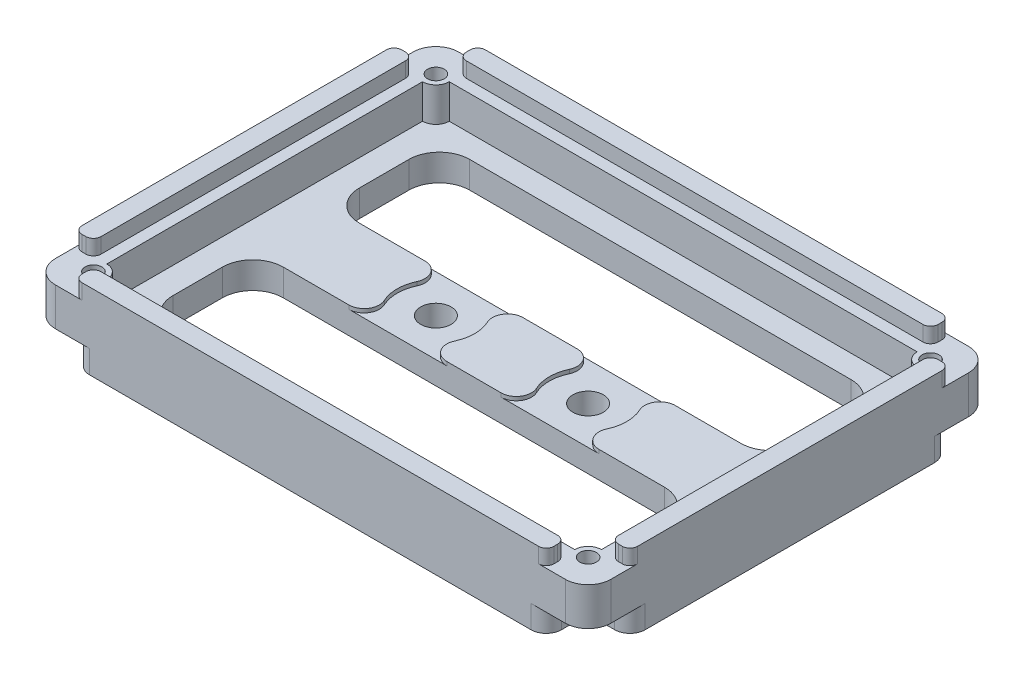
SolidWorks part; units mm, degrees
ref_plane "Plan de face" through (0, 0, 0) normal (0, 0, 1) x (1, 0, 0)
ref_plane "Plan de dessus" through (0, 0, 0) normal (0, 1, 0) x (1, 0, 0)
ref_plane "Plan de droite" through (0, 0, 0) normal (1, 0, 0) x (0, 0, -1)
sketch "Esquisse1" plane through (0, 0, 0) normal (0, 1, 0) x (1, 0, 0)
  line L1 (-32.5, -22.5) -> (32.5, -22.5) construction
  line L2 (-32.5, -22.5) -> (-32.5, 22.5) construction
  line L3 (-32.5, 22.5) -> (32.5, 22.5) construction
  line L4 (32.5, -22.5) -> (32.5, 22.5) construction
  line L5 (-32.5, -22.5) -> (32.5, 22.5) construction
  line L6 (-32.5, 22.5) -> (32.5, -22.5) construction
  line L7 (-31.0556, -21.5) -> (31.0556, -21.5)
  line L8 (-31.0556, -21.5) -> (-31.0556, 21.5)
  line L9 (-31.0556, 21.5) -> (31.0556, 21.5)
  line L10 (31.0556, -21.5) -> (31.0556, 21.5)
  line L11 (-31.0556, -21.5) -> (31.0556, 21.5) construction
  line L12 (-31.0556, 21.5) -> (31.0556, -21.5) construction
  line L13 (-36.5, -26.5) -> (36.5, -26.5)
  line L14 (-36.5, -26.5) -> (-36.5, 26.5)
  line L15 (-36.5, 26.5) -> (36.5, 26.5)
  line L16 (36.5, -26.5) -> (36.5, 26.5)
  line L17 (-36.5, -26.5) -> (36.5, 26.5) construction
  line L18 (-36.5, 26.5) -> (36.5, -26.5) construction
  circle A0 centre (-32.5, 22.5) radius 1.1
  circle A1 centre (32.5, 22.5) radius 1.1
  circle A2 centre (32.5, -22.5) radius 1.1
  circle A3 centre (-32.5, -22.5) radius 1.1
  point P0 (0, 0)
  point P10 (0, 0)
  point P15 (0, 0)
  dimension "D3" = 2.2
  dimension "D1" = 65
  dimension "D2" = 45
  dimension "D4" = 1
  dimension "D5" = 4
  dimension "D6" = 4
extrude "Boss.-Extru.1" add sketch "Esquisse1" along normal blind 10
sketch "Esquisse2" plane through (0, 0, 0) normal (0, -1, 0) x (1, 0, 0)
  line L1 (-36.5, -26.5) -> (36.5, -26.5)
  line L2 (-36.5, -26.5) -> (-36.5, 26.5)
  line L3 (-36.5, 26.5) -> (36.5, 26.5)
  line L4 (36.5, -26.5) -> (36.5, 26.5)
  line L5 (-36.5, -26.5) -> (36.5, 26.5) construction
  line L6 (-36.5, 26.5) -> (36.5, -26.5) construction
  point P0 (0, 0)
extrude "Boss.-Extru.2" add sketch "Esquisse2" against normal blind 4
sketch "Esquisse3" plane through (0, 0, 0) normal (0, -1, 0) x (1, 0, 0)
  line L1 (-36.5, 26.5) -> (-31, 26.5)
  line L2 (-36.5, 26.5) -> (-36.5, 21)
  line L3 (-36.5, 21) -> (-31, 21)
  line L4 (-31, 26.5) -> (-31, 21)
  line L5 (36.5, 26.5) -> (31, 26.5)
  line L6 (36.5, 26.5) -> (36.5, 21)
  line L7 (36.5, 21) -> (31, 21)
  line L8 (31, 26.5) -> (31, 21)
  line L9 (36.5, -26.5) -> (31, -26.5)
  line L10 (36.5, -26.5) -> (36.5, -21)
  line L11 (36.5, -21) -> (31, -21)
  line L12 (31, -26.5) -> (31, -21)
  line L13 (-36.5, -26.5) -> (-31, -26.5)
  line L14 (-36.5, -26.5) -> (-36.5, -21)
  line L15 (-36.5, -21) -> (-31, -21)
  line L16 (-31, -26.5) -> (-31, -21)
  dimension "D1" = 5.5
extrude "Enlèv. mat.-Extru.1" cut sketch "Esquisse3" against normal blind 3
sketch "Esquisse4" plane through (0, 4, 0) normal (0, 1, 0) x (1, 0, 0)
  circle A0 centre (-32.5, 22.5) radius 1.1
  circle A1 centre (32.5, 22.5) radius 1.1
  circle A2 centre (32.5, -22.5) radius 1.1
  circle A3 centre (-32.5, -22.5) radius 1.1
  dimension "D1" = 2.2
extrude "Enlèv. mat.-Extru.2" cut sketch "Esquisse4" against normal blind 5
fillet "Congé3" radius 3 4 edges at (-36.5, 6.5, 26.5) (-36.5, 6.5, -26.5) (36.5, 6.5, -26.5) (36.5, 6.5, 26.5)
sketch "Esquisse5" plane through (0, 4, 0) normal (0, 1, 0) x (1, 0, 0)
  line L0 (-10, 0) -> (10, 0) construction
  line L1 (31.0556, 21.5) -> (-31.0556, 21.5) construction
  line L2 (-29.0556, 5) -> (29.0556, 5)
  line L3 (-29.0556, 5) -> (-29.0556, 19.5)
  line L4 (-29.0556, 19.5) -> (29.0556, 19.5)
  line L5 (29.0556, 5) -> (29.0556, 19.5)
  line L6 (-29.0556, 5) -> (29.0556, 19.5) construction
  line L7 (-29.0556, 19.5) -> (29.0556, 5) construction
  line L8 (-29.0556, -5) -> (29.0556, -5)
  line L9 (-29.0556, -5) -> (-29.0556, -19.5)
  line L10 (-29.0556, -19.5) -> (29.0556, -19.5)
  line L11 (29.0556, -5) -> (29.0556, -19.5)
  line L12 (-29.0556, -5) -> (29.0556, -19.5) construction
  line L13 (-29.0556, -19.5) -> (29.0556, -5) construction
  line L14 (-31.0556, -21.5) -> (31.0556, -21.5) construction
  line L15 (-31.0556, 21.5) -> (-31.0556, -21.5) construction
  line L16 (31.0556, -21.5) -> (31.0556, 21.5) construction
  line L17 (31.0556, -21.5) -> (31.0556, 21.5) construction
  circle A0 centre (-10, 0) radius 2
  circle A1 centre (10, 0) radius 2
  point P3 (0, 0)
  point P6 (0, 12.25)
  point P11 (0, -12.25)
  dimension "D1" = 4
  dimension "D2" = 2
  dimension "D3" = 2
  dimension "D4" = 2
  dimension "D5" = 2
  dimension "D6" = 2
  dimension "D7" = 2
  dimension "D8" = 5
  dimension "D9" = 5
  dimension "D10" = 20
extrude "Enlèv. mat.-Extru.3" cut sketch "Esquisse5" against normal blind 5
fillet "Congé4" radius 4 8 edges at (-29.0556, 2, 19.5) (29.0556, 2, 5) (29.0556, 2, 19.5) (-29.0556, 2, 5) (29.0556, 2, -5) (29.0556, 2, -19.5) (-29.0556, 2, -19.5) (-29.0556, 2, -5)
fillet "Congé5" radius 2 12 edges at (-31, 1.5, -21) (-31, 1.5, 21) (31, 1.5, 21) (31, 1.5, -21) (-36.5, 1.5, 21) (-31, 1.5, 26.5) (31, 1.5, 26.5) (36.5, 1.5, 21) (36.5, 1.5, -21) (31, 1.5, -26.5) (-31, 1.5, -26.5) (-36.5, 1.5, -21)
sketch "Esquisse6" plane through (0, 4, 0) normal (0, 1, 0) x (1, 0, 0)
  circle A0 centre (-10, 0) radius 5.1
  circle A1 centre (10, 0) radius 5.1
  dimension "D1" = 10.2
extrude "Enlèv. mat.-Extru.6" cut sketch "Esquisse6" against normal blind 1
fillet "Congé6" radius 2 8 edges at (8.995, 3.5, 5) (8.995, 3.5, -5) (11.005, 3.5, -5) (11.005, 3.5, 5) (-11.005, 3.5, 5) (-8.995, 3.5, 5) (-11.005, 3.5, -5) (-8.995, 3.5, -5)
sketch "Esquisse7" plane through (0, 10, 0) normal (0, 1, 0) x (1, 0, 0)
  line L0 (-32.5, 20.7432) -> (-32.5, -20.7432)
  line L2 (-30.7432, -22.5) -> (30.7432, -22.5)
  line L4 (32.5, -20.7432) -> (32.5, 20.7432)
  line L6 (30.7432, 22.5) -> (-30.7432, 22.5)
  circle A0 centre (-32.5, 22.5) radius 1.7568 construction
  circle A1 centre (32.5, 22.5) radius 1.7568 construction
  circle A2 centre (-32.5, -22.5) radius 1.7568 construction
  circle A3 centre (32.5, -22.5) radius 1.7568 construction
  arc A4 (-30.7432, 22.5) -> (-32.5, 20.7432) centre (-32.5, 22.5) cw
  arc A5 (30.7432, 22.5) -> (32.5, 20.7432) centre (32.5, 22.5) ccw
  arc A6 (-32.5, -20.7432) -> (-30.7432, -22.5) centre (-32.5, -22.5) cw
  arc A7 (32.5, -20.7432) -> (30.7432, -22.5) centre (32.5, -22.5) ccw
  point P23 (30.7432, -22.4667)
  point P26 (0, 0)
extrude "Enlèv. mat.-Extru.7" cut sketch "Esquisse7" against normal blind 6.5
sketch "Esquisse8" plane through (0, 10, 0) normal (0, 1, 0) x (1, 0, 0)
  line L1 (-34, -24) -> (34, -24)
  line L2 (-34, -24) -> (-34, 24)
  line L3 (-34, 24) -> (34, 24)
  line L4 (34, -24) -> (34, 24)
  line L5 (-34, -24) -> (34, 24) construction
  line L6 (-34, 24) -> (34, -24) construction
  point P0 (0, 0)
  dimension "D1" = 68
  dimension "D2" = 48
extrude "Enlèv. mat.-Extru.8" cut sketch "Esquisse8" against normal blind 2
sketch "Esquisse9" plane through (0, 10, 0) normal (0, 1, 0) x (-1, 0, 0)
  line L0 (-36.5, 23.5) -> (-36.5, -23.5) construction
  line L1 (-36.5, 26.5) -> (-31, 26.5)
  line L2 (-36.5, 26.5) -> (-36.5, 21)
  line L3 (-36.5, 21) -> (-31, 21)
  line L4 (-31, 26.5) -> (-31, 21)
  line L5 (36.5, 26.5) -> (31, 26.5)
  line L6 (36.5, 26.5) -> (36.5, 21)
  line L7 (36.5, 21) -> (31, 21)
  line L8 (31, 26.5) -> (31, 21)
  line L9 (36.5, -26.5) -> (31, -26.5)
  line L10 (36.5, -26.5) -> (36.5, -21)
  line L11 (36.5, -21) -> (31, -21)
  line L12 (31, -26.5) -> (31, -21)
  line L13 (-36.5, -26.5) -> (-31, -26.5)
  line L14 (-36.5, -26.5) -> (-36.5, -21)
  line L15 (-36.5, -21) -> (-31, -21)
  line L16 (-31, -26.5) -> (-31, -21)
  line L17 (-33.5, -26.5) -> (33.5, -26.5) construction
  line L18 (33.5, 26.5) -> (-33.5, 26.5) construction
  line L19 (36.5, -23.5) -> (36.5, 23.5) construction
  point P20 (0, 0)
  point P25 (0, 0)
  point P26 (0, 0)
  point P27 (0, 0)
  dimension "D1" = 5.5
extrude "Enlèv. mat.-Extru.9" cut sketch "Esquisse9" against normal blind 2
fillet "Congé8" radius 1 16 edges at (-31, 9, 26.5) (-31, 9, 24) (31, 9, 26.5) (31, 9, 24) (36.5, 9, 21) (34, 9, 21) (31, 9, -26.5) (31, 9, -24) (34, 9, -21) (36.5, 9, -21) (-31, 9, -24) (-31, 9, -26.5) (-36.5, 9, -21) (-34, 9, -21) (-36.5, 9, 21) (-34, 9, 21)
